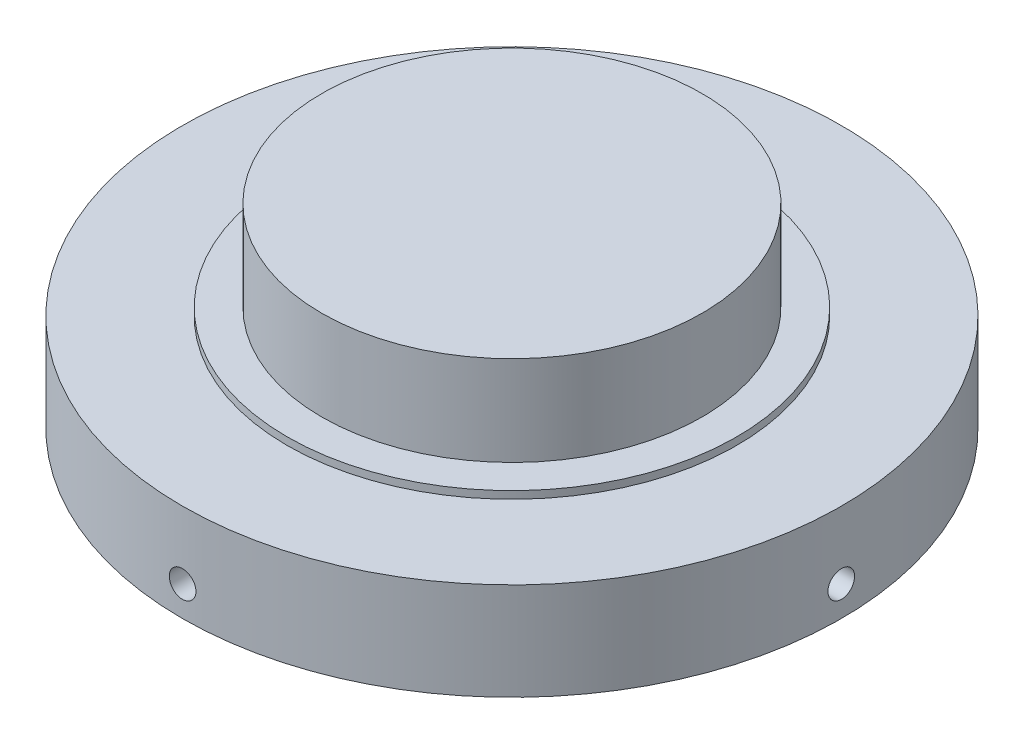
SolidWorks part; units mm, degrees
material "6061 合金"
ref_plane "前视基准面" through (0, 0, 0) normal (0, 0, 1) x (1, 0, 0)
ref_plane "上视基准面" through (0, 0, 0) normal (0, 1, 0) x (1, 0, 0)
ref_plane "右视基准面" through (0, 0, 0) normal (1, 0, 0) x (0, 0, -1)
sketch "草图1" plane through (0, 0, 0) normal (0, 1, 0) x (1, 0, 0)
  circle A0 centre (0, 0) radius 20 construction
sketch "草图2" plane through (0, 0, 0) normal (0, 1, 0) x (1, 0, 0)
  circle A2 centre (0, 0) radius 22
  circle A3 centre (0, 0) radius 22
  dimension "D1" = 2
extrude "凸台-拉伸1" add sketch "草图2" along normal blind 10
sketch "草图3" plane through (0, 0, 0) normal (0, -1, 0) x (1, 0, 0)
  circle A0 centre (0, 0) radius 20 construction
  circle A1 centre (0, 0) radius 20
extrude "切除-拉伸1" cut sketch "草图3" against normal blind 4
sketch "草图4" plane through (0, 10, 0) normal (0, 1, 0) x (1, 0, 0)
  circle A0 centre (0, 0) radius 12.7
  circle A1 centre (0, 0) radius 22 construction
  circle A2 centre (0, 0) radius 22
extrude "切除-拉伸2" cut sketch "草图4" against normal blind 3
ref_plane "基准面1" through (0, 0, -22) normal (0, 0, -1) x (-1, 0, 0)
sketch "草图5" plane through (0, 0, -22) normal (0, 0, -1) x (-1, 0, 0)
  line L0 (0, 0) -> (0, 2) construction
  line L1 (0, 5.5) -> (0, -5.5) construction
  dimension "D1" = 2
sketch "草图9" plane through (0, 0, 0) normal (0, -1, 0) x (1, 0, 0)
  circle A4 centre (0, 0) radius 20.15
  circle A5 centre (0, 0) radius 20.15
  dimension "D1" = 0.15
extrude "切除-拉伸3" cut sketch "草图9" against normal up to surface (4 mm away) up to face at (0, 4, -20)
sketch "草图10" plane through (0, 7, 0) normal (0, 1, 0) x (1, 0, 0)
  circle A0 centre (0, 0) radius 15
  circle A1 centre (0, 0) radius 22 construction
  circle A2 centre (0, 0) radius 22
  dimension "D1" = 30
extrude "切除-拉伸4" cut sketch "草图10" against normal blind 0.5
hole_wizard "#2-56 螺纹孔1" positions "3D草图2" profile "草图7" tap size "#2-56" standard "ANSI Inch"
sketch3d "3D草图2"
  point P0 (0, 2, -22)
  point P5 (0, 2, -22)
cosmetic thread "孔螺蚊线9" parameters "D1"=1.89, "D2"=2.1844
sketch "草图7" plane through (0, 2, -22) normal (1, 0, 0) x (0, 1, 0)
  line L0 (0, 0) -> (0, 5.5342)
  line L1 (0, 5.5342) -> (0.889, 5)
  line L2 (0.889, 5) -> (0.889, 0)
  line L5 (0.889, 0) -> (0, 0)
  line L10 (0, 5.5342) -> (-0.889, 5) construction
  line L11 (0, -6.35) -> (0, 107.95) construction
  dimension "螺纹孔钻头直径" = 1.778
  dimension "螺纹孔钻头深度" = 5
  dimension "导头角度" = 118
ref_plane "基准面2" [suppressed] through (22, 0, 0) normal (1, 0, 0) x (0, 0, -1)
sketch "草图11" [suppressed] plane through (22, 0, 0) normal (1, 0, 0) x (0, 0, -1)
  line L0 (0, 0) -> (0, 2.1408) construction
  line L1 (0, 16.5) -> (0, -16.5) construction
  circle A0 centre (0, 2.1408) radius 0.475
pattern_circular "阵列(圆周)1" count 4 over 360 about axis through (0, 0, 0) along (0, 1, 0) of "#2-56 螺纹孔1"
cosmetic thread "孔螺蚊线11" parameters "D1"=1.8696, "D2"=2.1844
cosmetic thread "孔螺蚊线12" parameters "D1"=1.8696, "D2"=2.1844
cosmetic thread "孔螺蚊线13" parameters "D1"=1.8696, "D2"=2.1844
sketch "草图12" plane through (0, 10, 0) normal (0, 1, 0) x (1, 0, 0)
  circle A1 centre (0, 0) radius 12.7
  circle A2 centre (0, 0) radius 12.7
  dimension "D1" = 0
extrude "凸台-拉伸2" add sketch "草图12" along normal blind 3
